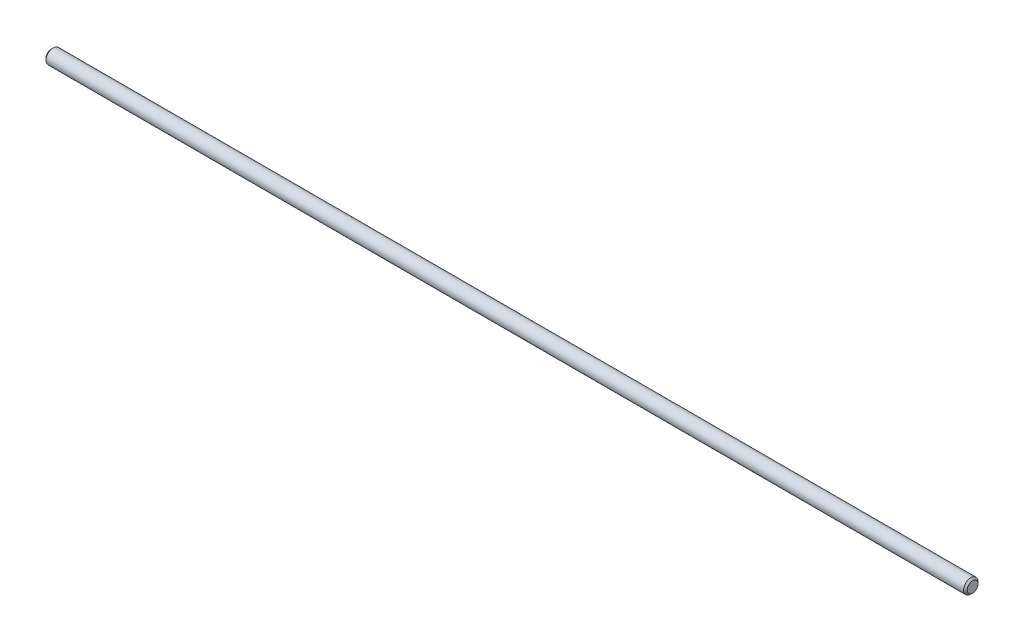
SolidWorks part; units mm, degrees
ref_plane "Front Plane" through (0, 0, 0) normal (0, 0, 1) x (1, 0, 0)
ref_plane "Top Plane" through (0, 0, 0) normal (0, 1, 0) x (1, 0, 0)
ref_plane "Right Plane" through (0, 0, 0) normal (1, 0, 0) x (0, 0, -1)
sketch "Sketch1" plane through (0, 0, 0) normal (0, 0, 1) x (1, 0, 0)
  line L0 (-38.1, 0) -> (38.1, 0) construction
  line L1 (38.1, 4.7625) -> (38.1, -4.7625) construction
  line L2 (-38.1, 4.7625) -> (-38.1, -4.7625) construction
  point P6 (32.5438, -4.7625)
  dimension "Thread Diameter" = 9.525
  dimension "Length" = 76.2
  dimension "D1" = 5.5562
sketch "Sketch2" plane through (0, 0, 0) normal (1, 0, 0) x (0, 0, -1)
  circle A0 centre (0, 0) radius 4.7625
extrude "Boss-Extrude1" add sketch "Sketch2" against normal blind 609.6
sketch "Sketch3" plane through (0, 0, 0) normal (1, 0, 0) x (0, 0, -1)
  circle A1 centre (0, 0) radius 4.7625
  circle A2 centre (0, 0) radius 4.7625
  dimension "D1" = 0
curve "Helix/Spiral1" pitch 1.5875 height 77.7875 turns 49 parameters "Pitch"=1.5875
chamfer "Chamfer1" distance 1.1906 angle 45 2 edges at (-609.6, 0, -4.7625) (0, 0, -4.7625)
sketch "Sketch4" plane through (0, 0, 0) normal (0, 0, 1) x (1, 0, 0)
  line L0 (38.0008, 4.9344) -> (38.7945, 3.5595) construction
  line L1 (38.7945, 3.5595) -> (39.5883, 4.9344) construction
  line L2 (39.5883, 4.9344) -> (38.0008, 4.9344) construction
  line L3 (38.7945, 4.9344) -> (38.7945, 4.7625) construction
  line L4 (38.7945, 3.5595) -> (38.7945, 3.7314) construction
  line L5 (38.6953, 3.7314) -> (38.8938, 3.7314) construction
  line L6 (38.1, 4.7625) -> (39.4891, 4.7625) construction
  line L7 (38.6953, 3.7314) -> (38.0504, 4.8484)
  line L8 (38.6953, 3.7314) -> (38.8938, 3.7314)
  line L9 (38.0504, 4.8484) -> (39.5387, 4.8484)
  line L10 (39.5387, 4.8484) -> (38.8938, 3.7314)
  point P13 (38.7945, 4.8484)
  dimension "D2" = 0.1984
sweep "Cut-Sweep3" [suppressed] cut profiles "Sketch4" path "Helix/Spiral1"
sketch "Sketch5" plane through (0, 0, 0) normal (1, 0, 0) x (0, 0, -1)
  circle A0 centre (0, 0) radius 4.7625 construction
  circle A1 centre (0, 0) radius 4.7625
extrude "Cut-Extrude1" [suppressed] cut sketch "Sketch5" against normal blind 304.8
equation "\"D3@Helix/Spiral1\" = \"Length@Sketch1\"+\"Pitch@Helix/Spiral1\""
equation "\"D1@Chamfer1\" = \"Pitch@Helix/Spiral1\"*.75"
equation "\"D1@Sketch4\" = \"Pitch@Helix/Spiral1\""
equation "\"D2@Sketch4\" = \"D1@Sketch4\"/8"
equation "\"D1@Sketch1\" = \"Pitch@Helix/Spiral1\"*3.50"
